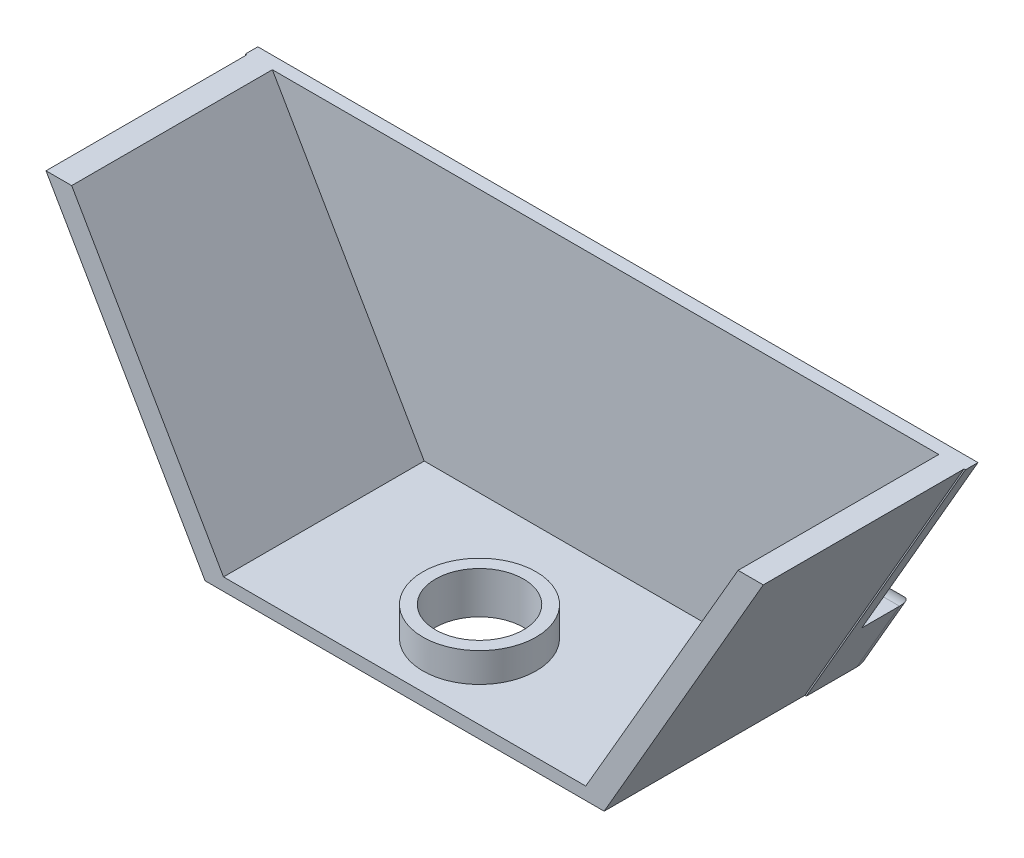
SolidWorks part; units mm, degrees
ref_plane "Front Plane" through (0, 0, 0) normal (0, 0, 1) x (1, 0, 0)
ref_plane "Top Plane" through (0, 0, 0) normal (0, 1, 0) x (1, 0, 0)
ref_plane "Right Plane" through (0, 0, 0) normal (1, 0, 0) x (0, 0, -1)
sketch "Sketch1" plane through (0, 0, 0) normal (0, 0, 1) x (1, 0, 0)
  line L0 (86.661, 23.4011) -> (29.4308, 23.4011)
  line L1 (29.4308, 23.4011) -> (42.0748, 1.5011)
  line L2 (42.0748, 1.5011) -> (74.0171, 1.5011)
  line L3 (74.0171, 1.5011) -> (86.661, 23.4011)
extrude "Boss-Extrude1" add sketch "Sketch1" along normal blind 1
sketch "Sketch2" plane through (0, 0, 0) normal (0, 0, -1) x (-1, 0, 0)
  line L0 (-74.0171, 1.5011) -> (-71.1171, 1.5011)
  line L1 (-42.0748, 1.5011) -> (-74.0171, 1.5011) construction
  line L2 (-71.1171, 1.5011) -> (-71.1171, 7.4011)
  line L3 (-71.1171, 7.4011) -> (-77.4234, 7.4011)
  line L4 (-74.0171, 1.5011) -> (-86.661, 23.4011) construction
  line L5 (-77.4234, 7.4011) -> (-74.0171, 1.5011)
  line L6 (-42.0748, 1.5011) -> (-44.9748, 1.5011)
  line L7 (-44.9748, 1.5011) -> (-44.9748, 7.4011)
  line L8 (-44.9748, 7.4011) -> (-38.6684, 7.4011)
  line L9 (-29.4308, 23.4011) -> (-42.0748, 1.5011) construction
  line L10 (-38.6684, 7.4011) -> (-42.0748, 1.5011)
extrude "Boss-Extrude2" add sketch "Sketch2" along normal blind 5
fillet "Fillet1" radius 2 6 edges at (44.9748, 4.4511, -5) (41.8216, 7.4011, -5) (40.3716, 4.4511, -5) (74.2702, 7.4011, -5) (71.1171, 4.4511, -5) (75.7202, 4.4511, -5)
sketch "Sketch4" plane through (0, 0, 1) normal (0, 0, 1) x (1, 0, 0)
  line L0 (42.1903, 1.5011) -> (73.9016, 1.5011)
  line L1 (29.5463, 23.4011) -> (42.1903, 1.5011)
  line L2 (29.5463, 23.4011) -> (31.5855, 23.4011)
  line L3 (86.661, 23.4011) -> (29.4308, 23.4011) construction
  line L4 (73.9016, 1.5011) -> (86.5456, 23.4011)
  line L5 (42.6521, 2.5011) -> (73.4397, 2.5011) construction
  line L6 (43.6521, 2.5011) -> (72.4397, 2.5011)
  line L11 (43.6521, 2.5011) -> (31.5855, 23.4011)
  line L12 (86.5456, 23.4011) -> (84.5456, 23.4011)
  line L13 (42.0748, 1.5011) -> (74.0171, 1.5011) construction
  line L14 (42.0748, 1.5011) -> (36.3013, 11.5011) construction
  line L15 (79.7906, 11.5011) -> (74.0171, 1.5011) construction
  line L16 (42.6521, 2.5011) -> (37.1673, 12.0011) construction
  line L17 (72.4397, 2.5011) -> (84.5456, 23.4011)
  line L19 (78.9245, 12.0011) -> (73.4397, 2.5011) construction
  dimension "D1" = 1
extrude "Boss-Extrude3" add sketch "Sketch4" along normal blind 15.95
sketch "Sketch10" plane through (0, 2.5011, 0) normal (0, 1, 0) x (1, 0, 0)
  line L0 (58.0459, -11) -> (72.4397, -11) construction
  line L1 (72.4397, -16.95) -> (72.4397, -1) construction
  circle A0 centre (58.0459, -11) radius 3.5
  circle A1 centre (58.0459, -11) radius 4.5
extrude "Boss-Extrude7" add sketch "Sketch10" along normal blind 2.33
sketch "Sketch13" plane through (0, 2.5011, 0) normal (0, 1, 0) x (1, 0, 0)
  circle A0 centre (58.0459, -11) radius 3.5
extrude "Cut-Extrude1" cut sketch "Sketch13" against normal blind 1
